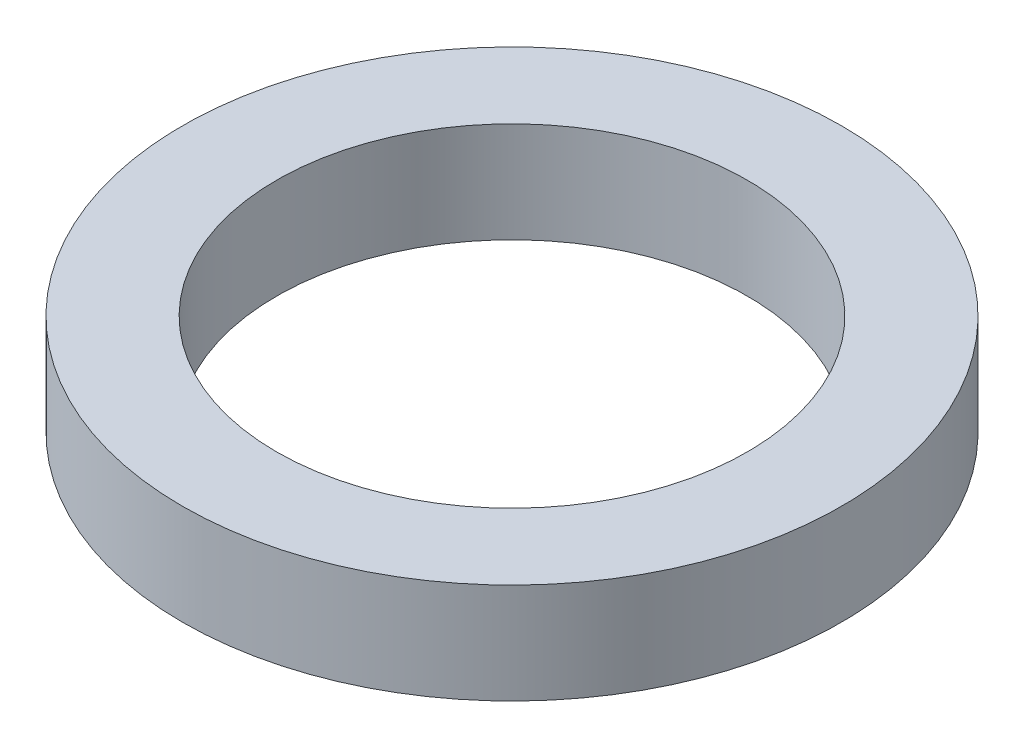
SolidWorks part; units mm, degrees
ref_plane "Front Plane" through (0, 0, 0) normal (0, 0, 1) x (1, 0, 0)
ref_plane "Top Plane" through (0, 0, 0) normal (0, 1, 0) x (1, 0, 0)
ref_plane "Right Plane" through (0, 0, 0) normal (1, 0, 0) x (0, 0, -1)
sketch "Sketch1" plane through (0, 0, 0) normal (0, 1, 0) x (1, 0, 0)
  circle A0 centre (0, 0) radius 52.5
  dimension "FLANGE_OD" = 105
extrude "Boss-Extrude1" add sketch "Sketch1" along normal blind 16
sketch "Sketch2" plane through (0, 0, 0) normal (0, 1, 0) x (1, 0, 0)
  circle A0 centre (0, 0) radius 37.5
  dimension "BORE_D" = 75
extrude "Cut-Extrude1" cut sketch "Sketch2" along normal through all
sketch "Sketch3" plane through (0, 16, 0) normal (0, 1, 0) x (1, 0, 0)
  circle A0 centre (0, 0) radius 23.2556 construction
  circle A1 centre (-23.2556, 0) radius 2.6991
  dimension "BOLT_D" = 5.3982
  dimension "BOLT_PCD" = 46.5112
extrude "Cut-Extrude2" cut sketch "Sketch3" against normal blind 10.0631 rebuild error yes
pattern_circular "CirPattern1" count 8 over 360 rebuild error yes
